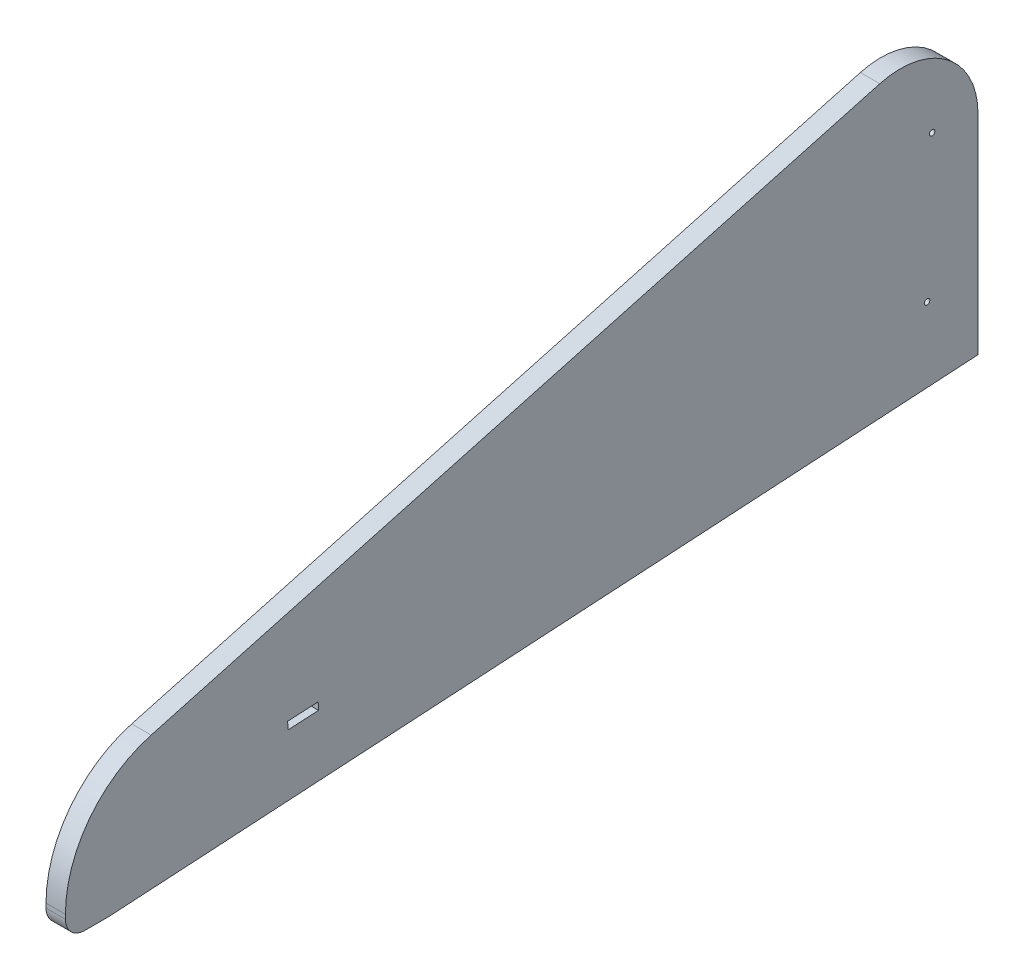
SolidWorks part; units mm, degrees
ref_plane "Front Plane" through (0, 0, 0) normal (0, 0, 1) x (1, 0, 0)
ref_plane "Top Plane" through (0, 0, 0) normal (0, 1, 0) x (1, 0, 0)
ref_plane "Right Plane" through (0, 0, 0) normal (1, 0, 0) x (0, 0, -1)
sketch "Sketch1" plane through (0, 0, 0) normal (1, 0, 0) x (0, 0, -1)
  line L0 (-60.2169, 47.5664) -> (-60.2169, -26.0345)
  line L1 (-60.2169, -26.0345) -> (-31.9898, -26.0345)
  line L3 (536.5906, 7.973) -> (536.5906, 211.173)
  line L4 (-60.2169, 47.5664) -> (536.5906, 211.173)
  line L5 (-31.9898, -26.0345) -> (536.5906, 7.973)
  circle A0 centre (503.3166, 54.5836) radius 1.778
  circle A1 centre (506.6186, 148.7021) radius 1.778
  circle A2 centre (-28.658, 27.3423) radius 1.778
  dimension "D1" = 203.2
  dimension "D2" = 48.514
  dimension "D4" = 52.324
  dimension "D3" = 33.274
  dimension "D5" = 29.972
extrude "Boss-Extrude1" add sketch "Sketch1" along normal blind 12.7 contours L0 L1 L5 L3 L4
fillet "Fillet1" radius 76.2 1 edges at (6.35, 47.5664, 60.2169)
fillet "Fillet2" radius 50.8 1 edges at (6.35, 211.173, -536.5906)
fillet "Fillet3" radius 12.7 1 edges at (6.35, -26.0345, 60.2169)
extrude "Cut-Extrude1" cut sketch "Sketch1<3>" along normal blind 32.004 contours A0
sketch "Sketch1<3>" plane through (0, 0, 0) normal (1, 0, 0) x (0, 0, -1) same geometry as "Sketch1"
extrude "Cut-Extrude3" cut sketch "Sketch1<5>" along normal blind 19.304 contours A1
sketch "Sketch1<5>" plane through (0, 0, 0) normal (1, 0, 0) x (0, 0, -1) same geometry as "Sketch1"
sketch "Sketch2" plane through (12.7, -3.6109, -1.6731) normal (1, 0, 0) x (0, 0.0523, -0.9986)
  line L2 (84.8791, 25.321) -> (104.8791, 25.321)
  line L3 (84.8791, 25.321) -> (84.8791, 20.321)
  line L4 (84.8791, 20.321) -> (104.8791, 20.321)
  line L5 (104.8791, 25.321) -> (104.8791, 20.321)
  line L6 (84.8791, 25.321) -> (104.8791, 20.321) construction
  line L7 (84.8791, 20.321) -> (104.8791, 25.321) construction
  point P0 (94.8791, 22.821)
  point P3 (94.8791, 22.821)
  dimension "D3" = 20
  dimension "D4" = 5
extrude "Cut-Extrude4" cut sketch "Sketch2" against normal blind 5
sketch "Sketch3" plane through (0, 0, 0) normal (-1, 0, 0) x (0, 0, 1)
  line L0 (-105.345, 22.1712) -> (-105.0833, 27.1644) construction
  line L1 (-85.3724, 21.1245) -> (-105.345, 22.1712) construction
  line L2 (-105.0833, 27.1644) -> (-85.1107, 26.1176) construction
  line L3 (-85.1107, 26.1176) -> (-85.3724, 21.1245) construction
  line L4 (-85.1107, 26.1176) -> (-85.3724, 21.1245)
  line L5 (-105.345, 22.1712) -> (-105.0833, 27.1644)
  line L6 (-105.0833, 27.1644) -> (-85.1107, 26.1176)
  line L7 (-85.3724, 21.1245) -> (-105.345, 22.1712)
extrude "Cut-Extrude5" cut sketch "Sketch3" against normal blind 5
